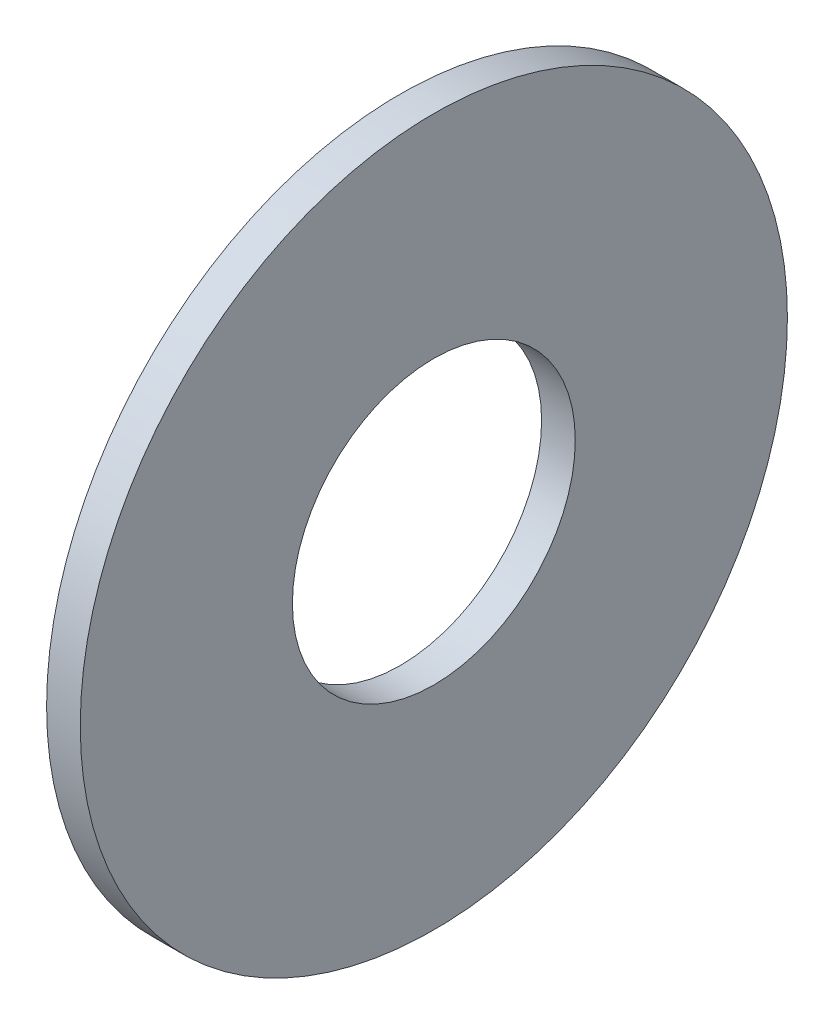
SolidWorks part; units mm, degrees
ref_plane "Plane1" through (0, 0, 0) normal (0, 0, 1) x (1, 0, 0)
ref_plane "Plane2" through (0, 0, 0) normal (0, 1, 0) x (1, 0, 0)
ref_plane "Plane3" through (0, 0, 0) normal (1, 0, 0) x (0, 0, -1)
sketch "Sketch1" plane through (0, 0, 0) normal (0, 0, 1) x (1, 0, 0)
  line L0 (-34.925, 0) -> (9.525, 0) construction
  line L1 (0, 4.2) -> (0, 10.5)
  line L2 (0, 10.5) -> (-1, 10.5)
  line L3 (-1, 10.5) -> (-1, 4.2)
  line L4 (-1, 4.2) -> (0, 4.2)
  dimension "Thickness" = 1
  dimension "Inside_dia" = 8.4
  dimension "Outside_dia" = 21
revolve "Base-Revolve" add sketch "Sketch1" angle 360 about L0
